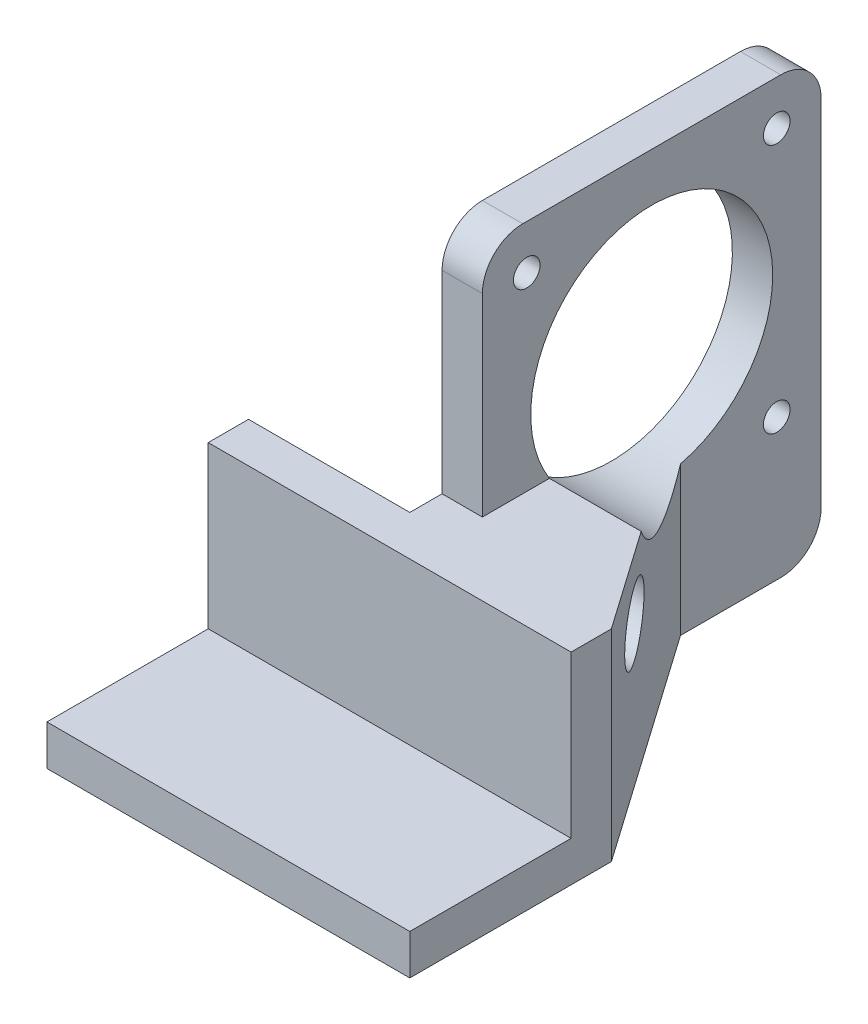
SolidWorks part; units mm, degrees
ref_plane "Front Plane" through (0, 0, 0) normal (0, 0, 1) x (1, 0, 0)
ref_plane "Top Plane" through (0, 0, 0) normal (0, 1, 0) x (1, 0, 0)
ref_plane "Right Plane" through (0, 0, 0) normal (1, 0, 0) x (0, 0, -1)
sketch "Sketch1" plane through (0, 0, 0) normal (0, 0, 1) x (1, 0, 0)
  line L1 (0, 0) -> (45, 0)
  line L2 (0, 0) -> (0, 25)
  line L3 (0, 25) -> (45, 25)
  line L4 (45, 0) -> (45, 25)
  dimension "D1" = 45
  dimension "D2" = 25
extrude "Boss-Extrude1" add sketch "Sketch1" along normal blind 5
sketch "Sketch2" plane through (0, 0, 0) normal (0, 0, -1) x (-1, 0, 0)
  line L1 (-25, 25) -> (-20, 25)
  line L2 (-25, 25) -> (-25, 0)
  line L3 (-25, 0) -> (-20, 0)
  line L4 (-20, 25) -> (-20, 0)
  line L5 (-45, 25) -> (0, 25) construction
  line L7 (0, 25) -> (0, 0) construction
  dimension "D1" = 5
  dimension "D2" = 20
extrude "Boss-Extrude2" add sketch "Sketch2" along normal blind 46
sketch "Sketch3" plane through (0, 0, 5) normal (0, 0, 1) x (1, 0, 0)
  line L0 (0, 25) -> (0, 0) construction
  line L1 (45, 0) -> (0, 0)
  line L2 (45, 0) -> (45, 5)
  line L3 (45, 5) -> (0, 5)
  line L4 (0, 0) -> (0, 5)
  dimension "D1" = 5
extrude "Boss-Extrude3" add sketch "Sketch3" along normal blind 20
chamfer "Chamfer2" distance 20 angle 55 1 edges at (25, 12.5, 0) first distance on face at (35, 12.5, 0)
chamfer "Chamfer3" distance 20 angle 55 1 edges at (20, 12.5, 0) first distance on face at (10, 12.5, 0)
sketch "Sketch4" plane through (0, 25, 0) normal (0, 1, 0) x (1, 0, 0)
  line L1 (20, 46) -> (25, 46)
  line L2 (20, 46) -> (20, 4)
  line L3 (20, 4) -> (25, 4)
  line L4 (25, 46) -> (25, 4)
  dimension "D1" = 42
  dimension "D2" = 5
extrude "Boss-Extrude4" add sketch "Sketch4" along normal blind 29
sketch "Sketch6" plane through (25, 0, 0) normal (1, 0, 0) x (0, 0, -1)
  line L0 (4, 54) -> (46, 54) construction
  line L2 (46, 54) -> (46, 0) construction
  circle A0 centre (25, 33) radius 15
  dimension "D1" = 30
  dimension "D2" = 21
  dimension "D3" = 21
extrude "Cut-Extrude1" cut sketch "Sketch6" against normal through all both and the other way through all
sketch "Sketch7" plane through (20, 0, 0) normal (-1, 0, 0) x (0, 0, 1)
  line L1 (-46, 54) -> (0, 54)
  line L2 (-46, 54) -> (-46, 10)
  line L3 (-46, 10) -> (0, 10)
  line L4 (0, 54) -> (0, 10)
  line L5 (5, 25) -> (5, 5) construction
  dimension "D1" = 44
  dimension "D2" = 5
extrude "Cut-Extrude2" cut sketch "Sketch7" along normal through all
sketch "Sketch8" plane through (20, 0, 0) normal (-1, 0, 0) x (0, 0, 1)
  line L1 (-40.5, 17.5) -> (-9.5, 17.5) construction
  line L2 (-40.5, 17.5) -> (-40.5, 48.5) construction
  line L3 (-40.5, 48.5) -> (-9.5, 48.5) construction
  line L4 (-9.5, 17.5) -> (-9.5, 48.5) construction
  line L5 (-40.5, 17.5) -> (-9.5, 48.5) construction
  line L6 (-40.5, 48.5) -> (-9.5, 17.5) construction
  circle A0 centre (-40.5, 48.5) radius 1.65
  circle A1 centre (-9.5, 48.5) radius 1.65
  circle A2 centre (-9.5, 17.5) radius 1.65
  circle A3 centre (-40.5, 17.5) radius 1.65
  point P0 (-25, 33)
  dimension "D3" = 3.3
  dimension "D1" = 31
  dimension "D2" = 31
extrude "Cut-Extrude3" cut sketch "Sketch8" against normal through all
sketch "Sketch9" plane through (25, 0, 0) normal (1, 0, 0) x (0, 0, -1)
  circle A0 centre (9.5, 17.5) radius 4
  dimension "D1" = 8
extrude "Cut-Extrude4" cut sketch "Sketch9" along normal through all
fillet "Fillet1" radius 5 3 edges at (22.5, 0, -46) (22.5, 54, -4) (22.5, 54, -46)
